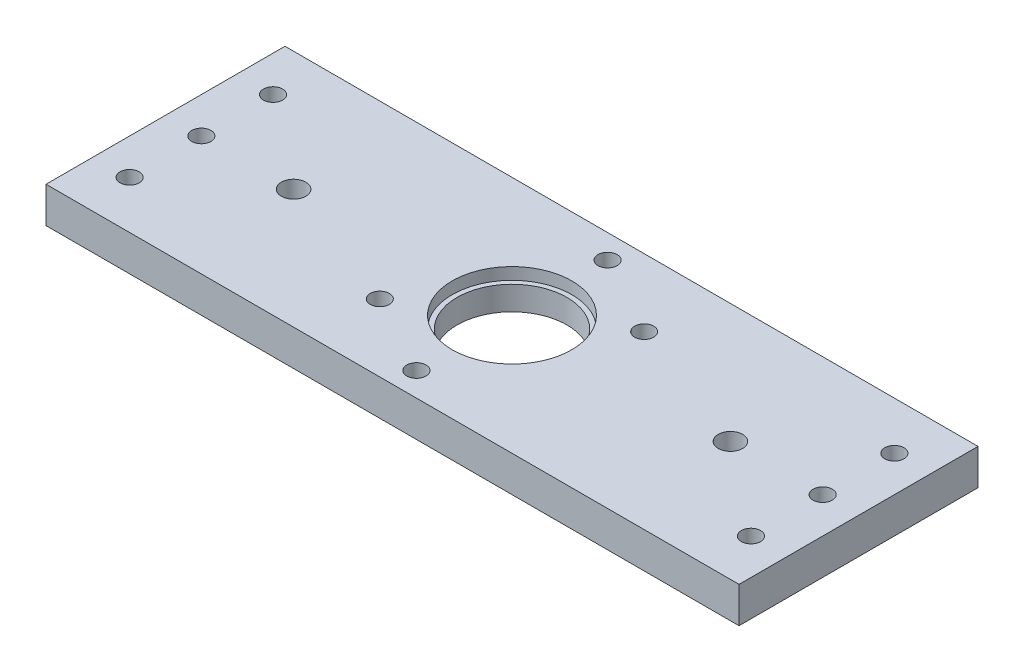
SolidWorks part; units mm, degrees
ref_plane "Front Plane" through (0, 0, 0) normal (0, 0, 1) x (1, 0, 0)
ref_plane "Top Plane" through (0, 0, 0) normal (0, 1, 0) x (1, 0, 0)
ref_plane "Right Plane" through (0, 0, 0) normal (1, 0, 0) x (0, 0, -1)
sketch "Sketch1" plane through (0, 0, 0) normal (0, 1, 0) x (1, 0, 0)
  line L1 (-92.075, -31.75) -> (92.075, -31.75)
  line L2 (-92.075, -31.75) -> (-92.075, 31.75)
  line L3 (-92.075, 31.75) -> (92.075, 31.75)
  line L4 (92.075, -31.75) -> (92.075, 31.75)
  line L5 (-92.075, -31.75) -> (92.075, 31.75) construction
  line L6 (-92.075, 31.75) -> (92.075, -31.75) construction
  point P0 (0, 0)
  dimension "D1" = 184.15
  dimension "D2" = 63.5
extrude "Boss-Extrude1" add sketch "Sketch1" along normal blind 9.525
sketch "Sketch2" plane through (0, 9.525, 0) normal (0, 1, 0) x (1, 0, 0)
  line L0 (-41.275, -31.75) -> (-41.275, 31.75)
  line L1 (-92.075, -31.75) -> (92.075, -31.75) construction
  line L2 (92.075, 31.75) -> (-92.075, 31.75) construction
  line L3 (-92.075, 31.75) -> (-92.075, -31.75) construction
  line L4 (41.275, 31.75) -> (41.275, -31.75)
  line L5 (92.075, -31.75) -> (92.075, 31.75) construction
  dimension "D1" = 50.8
  dimension "D2" = 50.8
sketch "Sketch3" plane through (0, 9.525, 0) normal (0, 1, 0) x (1, 0, 0)
  circle A0 centre (0, 0) radius 14.605
  dimension "D1" = 29.21
extrude "Cut-Extrude1" cut sketch "Sketch3" against normal through all
sketch "Sketch6" plane through (0, 0, 31.75) normal (0, 0, 1) x (1, 0, 0)
  line L0 (-41.275, 9.525) -> (-41.275, 0)
  line L1 (-92.075, 0) -> (92.075, 0) construction
sketch "Sketch7" plane through (0, 0, 0) normal (0, -1, 0) x (1, 0, 0)
  line L0 (-41.275, 31.75) -> (-41.275, -31.75)
  line L1 (92.075, -31.75) -> (-92.075, -31.75) construction
sketch "Sketch8" plane through (0, 0, 31.75) normal (0, 0, 1) x (1, 0, 0)
  line L0 (41.275, 9.525) -> (41.275, 0)
  line L1 (-92.075, 0) -> (92.075, 0) construction
  dimension "D1" = 82.55
  dimension "D2" = 82.55
sketch "Sketch9" plane through (0, 0, 0) normal (0, -1, 0) x (1, 0, 0)
  line L0 (41.275, 31.75) -> (41.275, -31.75)
  line L1 (92.075, -31.75) -> (-92.075, -31.75) construction
hole_wizard "#10 Clearance Hole1" positions "Sketch22" profile "Sketch23" hole size "#10" standard "ANSI Inch" end condition through all
sketch "Sketch22" plane through (0, 0, 0) normal (0, -1, 0) x (-1, 0, 0)
  point P0 (0, -25.4)
  point P2 (0, 25.4)
  dimension "D1" = 25.4
  dimension "D2" = 25.4
sketch "Sketch23" plane through (0, 0, 25.4) normal (1, 0, 0) x (0, 0, -1)
  line L0 (0, 0) -> (0, 9.525)
  line L1 (0, 9.525) -> (2.5527, 9.525)
  line L2 (2.5527, 9.525) -> (2.5527, 0)
  line L5 (2.5527, 0) -> (0, 0)
  line L11 (0, -6.35) -> (0, 107.95) construction
  dimension "Thru Hole Dia." = 5.1054
  dimension "Thru Hole Depth" = 9.525
hole_wizard "Ø6.5 (6.5) Diameter Hole3" positions "Sketch24" profile "Sketch25" hole size "Ø6.5" standard "ANSI Metric" end condition through all
sketch "Sketch24" plane through (0, 0, 0) normal (0, -1, 0) x (-1, 0, 0)
  line L0 (41.275, -31.75) -> (41.275, 31.75) construction
  line L1 (-41.275, 31.75) -> (-41.275, -31.75) construction
  point P0 (58.039, 0)
  point P2 (-58.039, 0)
  dimension "D1" = 16.764
  dimension "D2" = 16.764
sketch "Sketch25" plane through (-58.039, 0, 0) normal (1, 0, 0) x (0, 0, -1)
  line L0 (0, 0) -> (0, 9.525)
  line L1 (0, 9.525) -> (3.25, 9.525)
  line L2 (3.25, 9.525) -> (3.25, 0)
  line L5 (3.25, 0) -> (0, 0)
  line L11 (0, -6.35) -> (0, 107.95) construction
  dimension "Thru Hole Dia." = 6.5
  dimension "Thru Hole Depth" = 9.525
sketch "Sketch29" plane through (0, 9.525, 0) normal (0, 1, 0) x (1, 0, 0)
  circle A0 centre (0, 0) radius 15.875
extrude "Cut-Extrude5" cut sketch "Sketch29" against normal blind 3.175
hole_wizard "#10 Clearance Hole2" positions "Sketch32" profile "Sketch31" hole size "#10" standard "ANSI Inch" end condition through all
sketch "Sketch32" plane through (0, 9.525, 0) normal (0, 1, 0) x (1, 0, 0)
  line L0 (92.075, 31.75) -> (-92.075, 31.75) construction
  line L1 (-92.075, 31.75) -> (-92.075, -31.75) construction
  line L2 (-92.075, -31.75) -> (92.075, -31.75) construction
  line L3 (92.075, -31.75) -> (92.075, 31.75) construction
  point P0 (-82.55, 19.05)
  point P2 (-82.55, -19.05)
  point P4 (82.55, -19.05)
  point P6 (82.55, 19.05)
  point P17 (-82.55, 0)
  point P19 (82.55, 0)
  dimension "D1" = 12.7
  dimension "D2" = 9.525
  dimension "D3" = 9.525
  dimension "D4" = 12.7
  dimension "D5" = 9.525
  dimension "D6" = 12.7
  dimension "D7" = 9.525
  dimension "D8" = 12.7
sketch "Sketch31" plane through (-82.55, 9.525, -19.05) normal (1, 0, 0) x (0, 0, 1)
  line L0 (0, 0) -> (0, 9.525)
  line L1 (0, 9.525) -> (2.5527, 9.525)
  line L2 (2.5527, 9.525) -> (2.5527, 0)
  line L5 (2.5527, 0) -> (0, 0)
  line L11 (0, -6.35) -> (0, 107.95) construction
  dimension "Thru Hole Dia." = 5.1054
  dimension "Thru Hole Depth" = 9.525
sketch "Sketch36" plane through (0, 0, 0) normal (0, -1, 0) x (1, 0, 0)
  line L0 (-92.075, 31.75) -> (92.075, 31.75) construction
  line L1 (92.075, -31.75) -> (-92.075, -31.75) construction
  circle A0 centre (-21.3292, 13.7922) radius 2.54
  circle A1 centre (21.3292, -13.7922) radius 2.54
  dimension "D1" = 25.4
  dimension "D2" = 5.08
  dimension "D4" = 5.08
  dimension "D3" = 17.9578
  dimension "D5" = 50.8
  dimension "D6" = 17.9578
extrude "Cut-Extrude6" cut sketch "Sketch36" against normal through all
